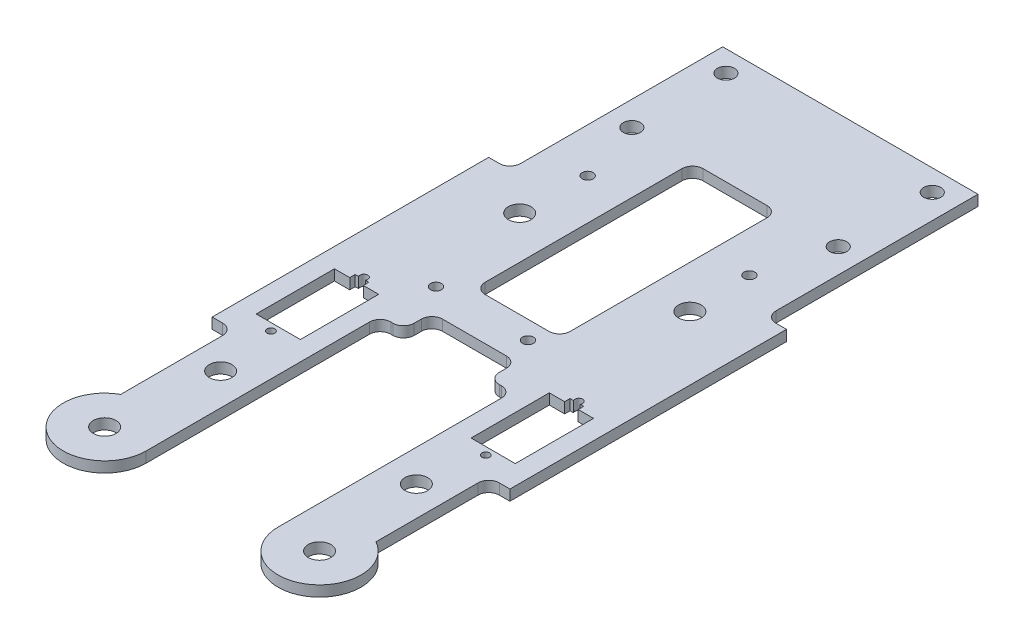
SolidWorks part; units mm, degrees
material "6061-T4 (SS)"
ref_plane "Front Plane" through (0, 0, 0) normal (0, 0, 1) x (1, 0, 0)
ref_plane "Top Plane" through (0, 0, 0) normal (0, 1, 0) x (1, 0, 0)
ref_plane "Right Plane" through (0, 0, 0) normal (1, 0, 0) x (0, 0, -1)
sketch "Sketch1" plane through (0, 0, 0) normal (0, 1, 0) x (1, 0, 0)
  line L1 (-44.45, -114.3) -> (44.45, -114.3)
  line L2 (-44.45, -114.3) -> (-44.45, 114.3)
  line L3 (-44.45, 114.3) -> (44.45, 114.3)
  line L4 (44.45, -114.3) -> (44.45, 114.3)
  line L5 (-44.45, -114.3) -> (44.45, 114.3) construction
  line L6 (-44.45, 114.3) -> (44.45, -114.3) construction
  point P0 (0, 0)
  dimension "D1" = 88.9
  dimension "D2" = 228.6
extrude "Boss-Extrude1" add sketch "Sketch1" along normal blind 3.175
sketch "Sketch11" plane through (0, 3.175, 0) normal (0, 1, 0) x (1, 0, 0)
  line L0 (0, 31.75) -> (97.4414, 31.75) construction
  line L10 (0, 0) -> (0, 114.3) construction
  line L14 (44.45, 114.3) -> (-44.45, 114.3) construction
  line L15 (0, 0) -> (117.475, 0) construction
  circle A0 centre (-26.289, 4.9828) radius 1.25
  circle A1 centre (-25.019, 53.1832) radius 1.25
  circle A2 centre (25.781, 38.1972) radius 1.25
  circle A3 centre (25.781, 10.0628) radius 1.25
  dimension "D3" = 2.5
  dimension "D5" = 2.5
  dimension "D7" = 31.75
  dimension "D9" = 25.781
  dimension "D4" = 2.5
  dimension "D6" = 2.5
  dimension "D2" = 25.019
  dimension "D8" = 26.289
  dimension "D10" = 6.4472
  dimension "D11" = 25.781
  dimension "D12" = 21.6872
  dimension "D13" = 26.7672
  dimension "D14" = 21.4332
extrude "Cut-Extrude12" [suppressed] cut sketch "Sketch11" against normal through all
sketch "Sketch18" plane through (0, 3.175, 0) normal (0, 1, 0) x (1, 0, 0)
  line L0 (44.45, 79.883) -> (-44.45, 79.883) construction
  line L1 (44.45, -114.3) -> (44.45, 114.3) construction
  line L2 (-44.45, 114.3) -> (-44.45, -114.3) construction
  line L3 (44.45, 114.3) -> (-44.45, 114.3) construction
  line L4 (0, 79.883) -> (0, -114.3) construction
  line L5 (-44.45, -114.3) -> (44.45, -114.3) construction
  line L6 (19.05, 79.883) -> (19.05, 6.35) construction
  line L7 (-19.05, 79.883) -> (-19.05, 6.35) construction
  line L8 (19.05, 6.35) -> (-19.05, 6.35) construction
  circle A0 centre (-24.9364, 60.833) radius 1.6319
  circle A1 centre (24.9365, 59.2455) radius 1.6319
  circle A2 centre (-18.9039, 9.525) radius 1.632
  circle A3 centre (8.6805, 9.398) radius 1.632
  dimension "D4" = 3.2639
  dimension "D9" = 3.2639
  dimension "D11" = 3.2639
  dimension "D13" = 3.2639
  dimension "D1" = 34.417
  dimension "D2" = 19.05
  dimension "D3" = 73.533
  dimension "D5" = 24.9365
  dimension "D6" = 19.05
  dimension "D7" = 24.9365
  dimension "D8" = 1.5875
  dimension "D10" = 6.0325
  dimension "D12" = 51.308
  dimension "D14" = 0.127
  dimension "D15" = 27.5844
sketch "Sketch12" plane through (0, 3.175, 0) normal (0, 1, 0) x (1, 0, 0)
  line L0 (0, 0) -> (44.45, 0) construction
  line L1 (44.45, -114.3) -> (44.45, 114.3) construction
  line L2 (0, 0) -> (0, 114.3) construction
  line L3 (44.45, 114.3) -> (-44.45, 114.3) construction
  line L4 (44.45, -44.45) -> (-44.45, -44.45) construction
  line L5 (-19.685, -69.85) -> (19.685, -69.85)
  line L6 (-19.685, -69.85) -> (-19.685, -6.35)
  line L7 (-19.685, -6.35) -> (19.685, -6.35)
  line L8 (19.685, -69.85) -> (19.685, -6.35)
  line L9 (-19.685, -69.85) -> (19.685, -6.35) construction
  line L10 (-19.685, -6.35) -> (19.685, -69.85) construction
  line L11 (-44.45, 114.3) -> (-44.45, -114.3) construction
  line L12 (0, -38.1) -> (0, -114.3) construction
  line L13 (-44.45, -114.3) -> (44.45, -114.3) construction
  circle A0 centre (29.21, -44.45) radius 3.3782
  circle A1 centre (-29.21, -44.45) radius 3.3782
  point P5 (0, -38.1)
  dimension "D5" = 6.7564
  dimension "D1" = 63.5
  dimension "D2" = 38.1
  dimension "D3" = 39.37
  dimension "D4" = 25.4
  dimension "D6" = 58.42
extrude "Cut-Extrude13" cut sketch "Sketch12" against normal through all
sketch "Sketch13" plane through (0, 0, 0) normal (0, -1, 0) x (-1, 0, 0)
  line L0 (0, 114.3) -> (0, -114.3) construction
  line L1 (-44.45, 114.3) -> (44.45, 114.3) construction
  line L2 (44.45, -114.3) -> (-44.45, -114.3) construction
  line L3 (-38.1, 114.3) -> (-38.1, 53.975)
  line L4 (-41.275, 50.8) -> (-44.45, 50.8)
  line L5 (-44.45, -114.3) -> (-44.45, 114.3) construction
  line L6 (-38.1, 114.3) -> (-44.45, 114.3)
  line L7 (-44.45, 114.3) -> (-44.45, 50.8)
  line L8 (38.1, 114.3) -> (44.45, 114.3)
  line L9 (38.1, 114.3) -> (38.1, 53.975)
  line L10 (41.275, 50.8) -> (44.45, 50.8)
  line L11 (44.45, 114.3) -> (44.45, 50.8)
  arc A0 (-38.1, 53.975) -> (-41.275, 50.8) centre (-41.275, 53.975) cw
  arc A1 (38.1, 53.975) -> (41.275, 50.8) centre (41.275, 53.975) ccw
  point P14 (-38.1, 50.8)
  dimension "D3" = 3.175
  dimension "D1" = 6.35
  dimension "D2" = 63.5
extrude "Cut-Extrude14" cut sketch "Sketch13" against normal through all
sketch "Sketch14" plane through (0, 0, 0) normal (0, -1, 0) x (-1, 0, 0)
  line L0 (0, 114.3) -> (0, 31.056) construction
  line L1 (-38.1, 114.3) -> (38.1, 114.3) construction
  line L2 (0, 114.3) -> (-38.1, 114.3) construction
  line L3 (-35.56, 114.3) -> (-35.56, 67.4804) construction
  line L4 (-38.1, 53.975) -> (-38.1, 114.3) construction
  line L5 (-26.035, 114.3) -> (-26.035, 67.4804) construction
  line L6 (-26.035, 107.95) -> (-35.56, 107.95) construction
  line L7 (-26.035, 93.9165) -> (-35.56, 93.9165) construction
  circle A0 centre (-30.7975, 107.95) radius 2.5527
  circle A1 centre (-30.7975, 79.883) radius 2.5527
  circle A2 centre (30.7975, 107.95) radius 2.5527
  circle A3 centre (30.7975, 79.883) radius 2.5527
  dimension "D4" = 5.1054
  dimension "D1" = 2.54
  dimension "D2" = 9.525
  dimension "D3" = 6.35
  dimension "D5" = 14.0335
extrude "Cut-Extrude15" cut sketch "Sketch14" against normal through all
sketch "Sketch15" plane through (0, 0, 0) normal (0, -1, 0) x (1, 0, 0)
  line L0 (44.45, 114.3) -> (44.45, -50.8) construction
  line L1 (-44.45, 114.3) -> (44.45, 114.3)
  line L2 (-44.45, 114.3) -> (-44.45, 57.15)
  line L3 (-44.45, 57.15) -> (44.45, 57.15)
  line L4 (44.45, 114.3) -> (44.45, 57.15)
  line L5 (19.685, 6.35) -> (-19.685, 6.35) construction
  line L6 (0, -36.7665) -> (0, -114.3) construction
  line L7 (12.7, -76.708) -> (12.7, -17.9917)
  line L8 (9.525, -14.8167) -> (-9.525, -14.8167)
  line L9 (38.1, -114.3) -> (-38.1, -114.3) construction
  line L10 (-12.7, -17.9917) -> (-12.7, -76.708)
  line L11 (9.525, -79.883) -> (-9.525, -79.883)
  line L12 (12.7, -76.708) -> (12.7, 6.35) construction
  line L13 (12.7, 6.35) -> (-12.7, 6.35) construction
  line L14 (-12.7, -76.708) -> (-12.7, 6.35) construction
  line L15 (12.7, -79.883) -> (-12.7, 6.35) construction
  line L16 (12.7, 6.35) -> (-12.7, -79.883) construction
  line L17 (12.7, 6.35) -> (-12.7, 6.35)
  line L18 (-12.7, 6.35) -> (-12.7, 1.0583)
  line L19 (-9.525, -2.1167) -> (9.525, -2.1167)
  line L20 (12.7, 1.0583) -> (12.7, 6.35)
  circle A0 centre (-29.21, 44.45) radius 3.3782 construction
  circle A1 centre (-30.7975, -79.883) radius 2.5527 construction
  arc A2 (-9.525, -79.883) -> (-12.7, -76.708) centre (-9.525, -76.708) cw
  arc A3 (9.525, -79.883) -> (12.7, -76.708) centre (9.525, -76.708) ccw
  arc A4 (12.7, -17.9917) -> (9.525, -14.8167) centre (9.525, -17.9917) ccw
  arc A5 (-9.525, -14.8167) -> (-12.7, -17.9917) centre (-9.525, -17.9917) ccw
  arc A6 (-12.7, 1.0583) -> (-9.525, -2.1167) centre (-9.525, 1.0583) ccw
  arc A7 (9.525, -2.1167) -> (12.7, 1.0583) centre (9.525, 1.0583) ccw
  point P35 (12.7, -14.8167)
  point P38 (-12.7, -14.8167)
  point P41 (-12.7, -2.1167)
  point P44 (12.7, -2.1167)
  dimension "D3" = 3.175
  dimension "D7" = 3.175
  dimension "D1" = 12.7
  dimension "D2" = 0
  dimension "D4" = 25.4
  dimension "D5" = 8.4667
  dimension "D6" = 12.7
extrude "Cut-Extrude16" cut sketch "Sketch15" against normal through all
fillet "Fillet1" radius 3.175 4 edges at (19.685, 1.5875, 6.35) (-19.685, 1.5875, 6.35) (-12.7, 1.5875, 6.35) (12.7, 1.5875, 6.35)
extrude "Cut-Extrude18" cut sketch "Sketch18" against normal through all
sketch "Sketch16" plane through (0, 3.175, 0) normal (0, 1, 0) x (1, 0, 0)
  line L0 (44.45, -57.15) -> (44.45, -76.2)
  line L1 (19.685, -57.15) -> (19.685, -76.2)
  line L2 (19.685, -76.2) -> (44.45, -76.2) construction
  line L3 (0, 0) -> (0, -94.827) construction
  line L4 (44.45, -57.15) -> (19.685, -57.15)
  line L5 (-19.685, -57.15) -> (-19.685, -76.2)
  line L6 (-44.45, -57.15) -> (-19.685, -57.15)
  line L7 (-44.45, -57.15) -> (-44.45, -76.2)
  arc A0 (44.45, -76.2) -> (19.685, -76.2) centre (32.0675, -76.2) cw
  arc A1 (-44.45, -76.2) -> (-19.685, -76.2) centre (-32.0675, -76.2) ccw
  circle A2 centre (32.0675, -76.2) radius 3.3782
  circle A3 centre (-32.0675, -76.2) radius 3.3782
  line M12 (-44.45, -57.15) -> (-19.685, -57.15)
  line M16 (19.685, -57.15) -> (44.45, -57.15)
  dimension "D2" = 6.7564
  dimension "D1" = 19.05
extrude "Boss-Extrude2" add sketch "Sketch16" against normal up to surface (3.175 mm away) contours L7 A1 L5 A3 M12 | A0 L0 L1 A2 M16 region at (32.0675, 3.175, 71.4304) region at (-32.0675, 3.175, 71.4304) up to face at (-24.9364, 0, -59.2011)
sketch "Sketch17" plane through (0, 3.175, 0) normal (0, 1, 0) x (1, 0, 0)
  line L0 (38.1, -65.3863) -> (38.1, -34.925)
  line L1 (44.45, -76.2) -> (44.45, 50.8) construction
  line L9 (0, 0) -> (0, -71.3802) construction
  line L15 (41.275, -31.75) -> (44.45, -31.75)
  line L20 (44.45, -31.75) -> (44.45, -76.2)
  line L21 (-41.275, -31.75) -> (-44.45, -31.75)
  line L22 (-38.1, -65.3863) -> (-38.1, -34.925)
  line L23 (-44.45, -31.75) -> (-44.45, -76.2)
  circle A4 centre (32.0675, -76.2) radius 3.3046 construction
  arc A5 (38.1, -34.925) -> (41.275, -31.75) centre (41.275, -34.925) cw
  circle A10 centre (32.0675, -76.2) radius 12.3825 construction
  arc A11 (38.1, -65.3863) -> (44.45, -76.2) centre (32.0675, -76.2) cw
  arc A12 (-38.1, -34.925) -> (-41.275, -31.75) centre (-41.275, -34.925) ccw
  arc A13 (-38.1, -65.3863) -> (-44.45, -76.2) centre (-32.0675, -76.2) ccw
  point P11 (38.1, -31.75)
  dimension "D2" = 3.175
  dimension "D3" = 44.45
  dimension "D1" = 6.35
extrude "Cut-Extrude17" cut sketch "Sketch17" against normal through all
sketch "Sketch19" plane through (0, 3.175, 0) normal (0, 1, 0) x (1, 0, 0)
  line L0 (0, 14.8167) -> (0, 79.883) construction
  line L1 (9.525, 14.8167) -> (-9.525, 14.8167) construction
  line L2 (-9.525, 79.883) -> (9.525, 79.883) construction
  line L3 (-12.7, 47.3498) -> (12.7, 47.3498) construction
  line L4 (-12.7, 17.9917) -> (-12.7, 76.708) construction
  line L5 (12.7, 76.708) -> (12.7, 17.9917) construction
  line L6 (-38.1, 53.975) -> (-12.7, 53.975) construction
  line L7 (-25.4, 53.975) -> (-25.4, 40.9998) construction
  circle A0 centre (-25.4, 40.9998) radius 3.3782
  circle A1 centre (25.4, 40.9998) radius 3.3782
  dimension "D1" = 6.7564
  dimension "D2" = 6.35
extrude "Cut-Extrude19" cut sketch "Sketch19" against normal through all
sketch "Sketch20" plane through (0, 3.175, 0) normal (0, 1, 0) x (1, 0, 0)
  line L0 (0, 0) -> (0, 61.1006) construction
  line L3 (-25.8445, 3.175) -> (-25.8445, -28.575) construction
  line L6 (-25.4635, -1.016) -> (-38.6715, -1.016) construction
  line L7 (-25.4635, -1.016) -> (-25.4635, -24.384)
  line L8 (-25.4635, -24.384) -> (-38.6715, -24.384)
  line L9 (-38.6715, -1.016) -> (-38.6715, -24.384)
  line L10 (-25.4635, -1.016) -> (-38.6715, -24.384) construction
  line L11 (-25.4635, -24.384) -> (-38.6715, -1.016) construction
  line L13 (-38.2905, 3.175) -> (-38.2905, -28.575) construction
  line L14 (-25.8445, 3.175) -> (-38.2905, -28.575) construction
  line L27 (-32.0675, -76.2) -> (-32.0675, 23.1424) construction
  line L28 (-38.2905, 3.175) -> (-25.8445, -28.575) construction
  line L29 (-38.2905, -28.575) -> (-32.9565, -28.575) construction
  line L30 (-32.9565, -28.575) -> (-32.9565, -27.305) construction
  line L31 (-31.1785, -28.575) -> (-31.1785, -27.305) construction
  line L32 (-25.8445, -28.575) -> (-31.1785, -28.575) construction
  line L33 (-25.8445, 3.175) -> (-31.1785, 3.175) construction
  line L34 (-31.1785, 3.175) -> (-31.1785, 1.905) construction
  line L35 (-32.9565, 3.175) -> (-32.9565, 1.905) construction
  line L36 (-38.2905, 3.175) -> (-32.9565, 3.175) construction
  line L38 (-30.0355, -1.016) -> (-30.0355, 0.6151)
  line L42 (-30.0355, -1.016) -> (-25.4635, -1.016)
  line L44 (-34.0995, -1.016) -> (-34.0995, 0.6151)
  line L45 (-34.0995, -1.016) -> (-38.6715, -1.016)
  line L47 (-33.0574, 0.6151) -> (-34.0995, 0.6151)
  line L48 (-32.0675, 1.1866) -> (-32.0675, 0.0436) construction
  line L49 (-32.0675, 1.1866) -> (-32.0675, 0.0436) construction
  line L50 (-32.0675, 0.6151) -> (-30.8266, 0.6151) construction
  line L51 (-30.0355, 0.6151) -> (-31.0776, 0.6151)
  line L52 (30.0355, -1.016) -> (30.0355, 0.6151)
  line L53 (30.0355, -1.016) -> (25.4635, -1.016)
  line L54 (25.4635, -1.016) -> (25.4635, -24.384)
  line L55 (25.4635, -24.384) -> (38.6715, -24.384)
  line L56 (38.6715, -1.016) -> (38.6715, -24.384)
  line L57 (34.0995, -1.016) -> (38.6715, -1.016)
  line L58 (34.0995, -1.016) -> (34.0995, 0.6151)
  line L59 (33.0574, 0.6151) -> (34.0995, 0.6151)
  line L60 (30.0355, 0.6151) -> (31.0776, 0.6151)
  arc A0 (-32.9565, -27.305) -> (-31.1785, -27.305) centre (-32.0675, -26.5866) cw construction
  arc A1 (-32.9565, 1.905) -> (-31.1785, 1.905) centre (-32.0675, 1.1866) ccw construction
  circle A2 centre (-32.0675, 1.1866) radius 1.143 construction
  circle A3 centre (-32.0675, -26.5866) radius 1.143
  circle A4 centre (32.0675, -26.5866) radius 1.143
  arc A7 (-33.0574, 0.6151) -> (-31.0776, 0.6151) centre (-32.0675, 1.1866) cw
  arc A8 (33.0574, 0.6151) -> (31.0776, 0.6151) centre (32.0675, 1.1866) ccw
  point P10 (-32.0675, -12.7)
  point P16 (-32.0675, -12.7)
  dimension "D1" = 13.208
  dimension "D2" = 23.368
  dimension "D3" = 63.5
  dimension "D4" = 2.032
extrude "Cut-Extrude20" cut sketch "Sketch20" against normal through all
sketch "Sketch21" plane through (0, 3.175, 0) normal (0, 1, 0) x (1, 0, 0)
  line L0 (0, 79.883) -> (-38.1, 79.883) construction
  line L1 (-9.525, 79.883) -> (9.525, 79.883) construction
  line L2 (-38.1, 114.3) -> (-38.1, 53.975) construction
  line L3 (-38.1, 114.3) -> (-38.1, 79.883) construction
  line L4 (-38.1, 97.0915) -> (48.4886, 97.0915) construction
  line L5 (5.1943, 79.883) -> (5.1943, 97.0915) construction
  circle A0 centre (22.3393, 97.0915) radius 2.5527
  circle A1 centre (-11.9507, 97.0915) radius 2.5527
  circle A3 centre (30.7975, 79.883) radius 2.5527 construction
  dimension "D1" = 5.1054
  dimension "D2" = 17.145
  dimension "D3" = 8.4582
extrude "Cut-Extrude21" [suppressed] cut sketch "Sketch21" against normal through all contours A1 | A0
